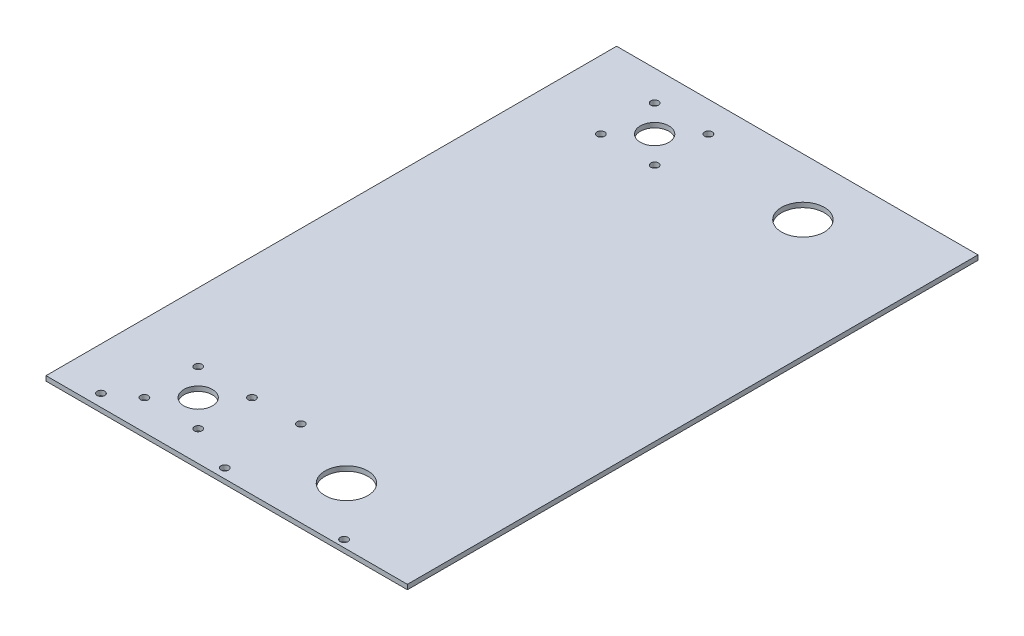
SolidWorks part; units mm, degrees
material "6061-T6 (SS)"
ref_plane "Front Plane" through (0, 0, 0) normal (0, 0, 1) x (1, 0, 0)
ref_plane "Top Plane" through (0, 0, 0) normal (0, 1, 0) x (1, 0, 0)
ref_plane "Right Plane" through (0, 0, 0) normal (1, 0, 0) x (0, 0, -1)
sketch "Sketch1" plane through (0, 0, 0) normal (0, 1, 0) x (1, 0, 0)
  line L1 (120.65, -190.5) -> (-120.65, -190.5)
  line L2 (120.65, -190.5) -> (120.65, 190.5)
  line L3 (120.65, 190.5) -> (-120.65, 190.5)
  line L4 (-120.65, -190.5) -> (-120.65, 190.5)
  line L5 (120.65, -190.5) -> (-120.65, 190.5) construction
  line L6 (120.65, 190.5) -> (-120.65, -190.5) construction
  point P0 (0, 0)
  dimension "D1" = 241.3
  dimension "D2" = 381
extrude "Boss-Extrude1" add sketch "Sketch1" along normal blind 3.175
sketch "Sketch6" plane through (0, 3.175, 0) normal (0, 1, 0) x (1, 0, 0)
  line L1 (-57.15, 152.4) -> (0, 0) construction
  line L2 (0, 0) -> (-57.15, -152.4) construction
  line L5 (-120.65, 190.5) -> (-120.65, -190.5) construction
  circle A0 centre (-57.15, -152.4) radius 38.1 construction
  circle A1 centre (-57.15, 152.4) radius 38.1 construction
  circle A2 centre (41.8592, -152.4) radius 38.1 construction
  circle A3 centre (41.8592, 152.4) radius 38.1 construction
  dimension "D1" = 76.2
  dimension "D5" = 228.6
  dimension "D3" = 99.0092
  dimension "D4" = 63.5
sketch "Sketch7" plane through (0, 3.175, 0) normal (0, 1, 0) x (1, 0, 0)
  circle A0 centre (41.8592, -152.4) radius 14.2875
  circle A1 centre (41.8592, 152.4) radius 14.2875
  circle A2 centre (-57.15, 152.4) radius 9.525
  circle A3 centre (-57.15, -152.4) radius 9.525
  circle A4 centre (-75.1105, 170.3605) radius 2.5527
  circle A5 centre (-57.15, 152.4) radius 25.4 construction
  circle A6 centre (-39.1895, 170.3605) radius 2.5527
  circle A7 centre (-39.1895, 134.4395) radius 2.5527
  circle A8 centre (-75.1105, 134.4395) radius 2.5527
  circle A9 centre (-57.15, -152.4) radius 25.4 construction
  circle A10 centre (-75.1105, -134.4395) radius 2.5527
  circle A11 centre (-39.1895, -134.4395) radius 2.5527
  circle A12 centre (-39.1895, -170.3605) radius 2.5527
  circle A13 centre (-75.1105, -170.3605) radius 2.5527
  point P24 (-57.15, 152.4)
  point P34 (-57.15, -152.4)
  dimension "D1" = 28.575
  dimension "D2" = 19.05
  dimension "D3" = 5.1054
  dimension "D5" = 50.8
  dimension "D4" = 4
  dimension "D6" = 4
extrude "Axle Holes" cut sketch "Sketch7" against normal through all
sketch "Sketch10" plane through (0, 3.175, 0) normal (0, 1, 0) x (1, 0, 0)
  circle A2 centre (-7.6454, -133.35) radius 2.5527 construction
  circle A10 centre (-92.075, -182.3949) radius 2.5527 construction
  circle A11 centre (-7.6454, -184.15) radius 2.5527 construction
  circle A12 centre (73.6092, -185.7375) radius 2.5527 construction
  circle A13 centre (-7.6454, -133.35) radius 2.5527
  circle A14 centre (-92.075, -182.3949) radius 2.5527
  circle A15 centre (-7.6454, -184.15) radius 2.5527
  circle A16 centre (73.6092, -185.7375) radius 2.5527
extrude "Cut-Extrude5" cut sketch "Sketch10" against normal through all
sketch "Sketch8" plane through (0, 3.175, 0) normal (0, 1, 0) x (1, 0, 0)
  circle A3 centre (38.8835, 28.8822) radius 19.8684
extrude "Cut-Extrude4" [suppressed] cut sketch "Sketch8" against normal through all
